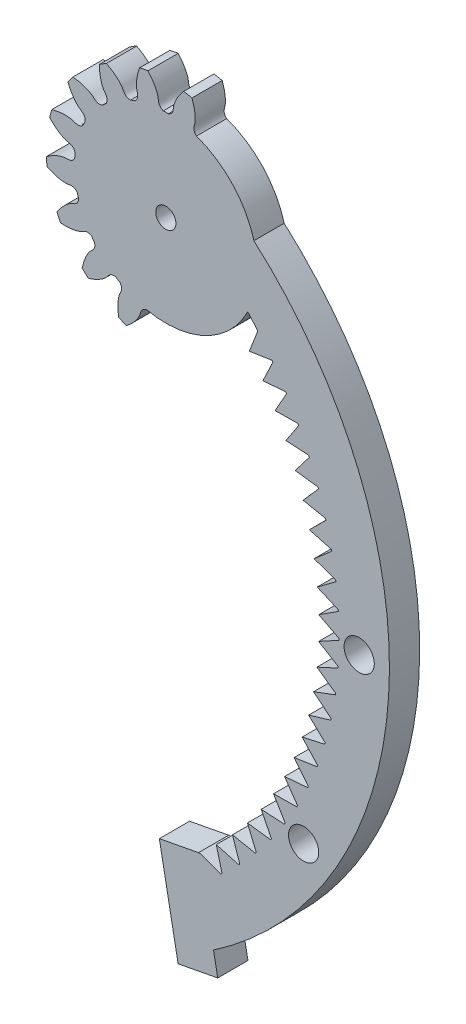
SolidWorks part; units mm, degrees
ref_plane "前视基准面" through (0, 0, 0) normal (0, 0, 1) x (1, 0, 0)
ref_plane "上视基准面" through (0, 0, 0) normal (0, 1, 0) x (1, 0, 0)
ref_plane "右视基准面" through (0, 0, 0) normal (1, 0, 0) x (0, 0, -1)
sketch "草图1" plane through (0, 0, 0) normal (0, 0, 1) x (1, 0, 0)
  circle A0 centre (0, 0) radius 11.875
extrude "凸台-拉伸1" add sketch "草图1" along normal blind 30
ref_axis "基准轴1" through (0, 0, -1.5) along (0, 0, 1)
sketch "草图2" plane through (0, 0, 0) normal (0, 0, 1) x (1, 0, 0)
  line L0 (0, 0) -> (0, 11.875) construction
  circle A0 centre (0, 0) radius 11.875 construction
  arc A1 (0.2521, 9.059) -> (-0.2521, 9.059) centre (0, 0) ccw
  arc A2 (3.8946, 13.4259) -> (-3.8946, 13.4259) centre (0, 0) ccw
  spline S0 degree 3 poles (0.2521, 9.059) (0.7848, 9.281) (0.7077, 9.6935) (0.7979, 10.081) (0.8062, 10.1139) (0.8163, 10.1505) (0.8282, 10.1907) (0.8421, 10.2345) (0.8582, 10.2818) (0.8766, 10.3324) (0.8974, 10.3865) (0.9208, 10.4438) (0.947, 10.5043) (0.976, 10.5679) (1.008, 10.6345) (1.0431, 10.704) (1.0815, 10.7763) (1.1232, 10.8513) (1.1685, 10.929) (1.2174, 11.0091) (1.27, 11.0916) (1.3265, 11.1763) (1.3869, 11.2632) (1.4514, 11.3521) (1.5201, 11.4429) (1.5931, 11.5354) (1.6704, 11.6295) (1.7522, 11.7251) (1.8386, 11.822) (1.9295, 11.9201) (2.0252, 12.0192) (2.1257, 12.1193) (2.2311, 12.22) (2.3414, 12.3213) (2.4567, 12.4231) (2.577, 12.5251) (2.7025, 12.6272) (2.8331, 12.7292) (2.969, 12.831) (3.1101, 12.9323) (3.2564, 13.0331) (3.4081, 13.1332) (3.6198, 13.2668) (3.7832, 13.3632) (3.8946, 13.4259) knots 0 0 0 0 0.193883 0.199024 0.204851 0.211363 0.21856 0.226443 0.235011 0.244265 0.254205 0.264829 0.27614 0.288136 0.300817 0.314184 0.328236 0.342973 0.358397 0.374505 0.391299 0.408779 0.426944 0.445795 0.465331 0.485552 0.506459 0.528051 0.550329 0.573293 0.596941 0.621276 0.646296 0.672001 0.698392 0.725468 0.753229 0.781677 0.810809 0.840627 0.871131 0.90232 0.934195 1 1 1 1
  spline S1 degree 3 poles (-0.2521, 9.059) (-0.7848, 9.281) (-0.7077, 9.6935) (-0.7979, 10.081) (-0.8062, 10.1139) (-0.8163, 10.1505) (-0.8282, 10.1907) (-0.8421, 10.2345) (-0.8582, 10.2818) (-0.8766, 10.3324) (-0.8974, 10.3865) (-0.9208, 10.4438) (-0.947, 10.5043) (-0.976, 10.5679) (-1.008, 10.6345) (-1.0431, 10.704) (-1.0815, 10.7763) (-1.1232, 10.8513) (-1.1685, 10.929) (-1.2174, 11.0091) (-1.27, 11.0916) (-1.3265, 11.1763) (-1.3869, 11.2632) (-1.4514, 11.3521) (-1.5201, 11.4429) (-1.5931, 11.5354) (-1.6704, 11.6295) (-1.7522, 11.7251) (-1.8386, 11.822) (-1.9295, 11.9201) (-2.0252, 12.0192) (-2.1257, 12.1193) (-2.2311, 12.22) (-2.3414, 12.3213) (-2.4567, 12.4231) (-2.577, 12.5251) (-2.7025, 12.6272) (-2.8331, 12.7292) (-2.969, 12.831) (-3.1101, 12.9323) (-3.2564, 13.0331) (-3.4081, 13.1332) (-3.6198, 13.2668) (-3.7832, 13.3632) (-3.8946, 13.4259) knots 0 0 0 0 0.193883 0.199024 0.204851 0.211363 0.21856 0.226443 0.235011 0.244265 0.254205 0.264829 0.27614 0.288136 0.300817 0.314184 0.328236 0.342973 0.358397 0.374505 0.391299 0.408779 0.426944 0.445795 0.465331 0.485552 0.506459 0.528051 0.550329 0.573293 0.596941 0.621276 0.646296 0.672001 0.698392 0.725468 0.753229 0.781677 0.810809 0.840627 0.871131 0.90232 0.934195 1 1 1 1
extrude "切除-拉伸1" cut sketch "草图2" along normal through all
pattern_circular "阵列(圆周)1" count 17 every 21.176 about axis through (0, 0, -1.5) along (0, 0, 1) of "切除-拉伸1"
sketch "草图3" plane through (0, 0, 0) normal (0, 0, 1) x (1, 0, 0)
  circle A0 centre (0, 0) radius 10.625 construction
  dimension "Dn" = 21.25
sketch "草图4" plane through (0, 0, 0) normal (0, 1, 0) x (1, 0, 0)
  line L0 (6.2893, -30) -> (9.2176, -30) construction
  line L1 (-17.9431, 27) -> (17.9431, 27)
  line L2 (-17.9431, 27) -> (-17.9431, -27)
  line L3 (-17.9431, -27) -> (17.9431, -27)
  line L4 (17.9431, 27) -> (17.9431, -27)
  line L5 (-17.9431, 27) -> (17.9431, -27) construction
  line L6 (-17.9431, -27) -> (17.9431, 27) construction
  point P0 (0, 0)
  dimension "D1" = 3
extrude "切除-拉伸2" cut sketch "草图4" against normal through all both and the other way through all
sketch "草图5" plane through (0, 0, 27) normal (0, 0, -1) x (-1, 0, 0)
  arc A0 (-3.5076, 8.3562) -> (1.4168, -8.9511) centre (0, 0) ccw
  arc A34 (-1.9124, -8.8584) -> (-1.4168, -8.9511) centre (0, 0) ccw
  arc A35 (-0.4197, -11.8676) -> (0.4197, -11.8676) centre (0, 0) ccw
  arc A36 (1.4168, -8.9511) -> (1.9124, -8.8584) centre (0, 0) ccw
  arc A37 (3.8958, -11.2178) -> (4.6784, -10.9146) centre (0, 0) ccw
  arc A38 (4.5546, -7.8348) -> (4.9833, -7.5694) centre (0, 0) ccw
  arc A39 (7.685, -9.053) -> (8.3053, -8.4875) centre (0, 0) ccw
  arc A40 (7.0773, -5.6605) -> (7.3812, -5.2581) centre (0, 0) ccw
  arc A41 (10.4364, -5.6655) -> (10.8105, -4.9142) centre (0, 0) ccw
  arc A42 (8.6442, -2.7216) -> (8.7822, -2.2366) centre (0, 0) ccw
  arc A43 (11.7782, -1.5129) -> (11.8557, -0.6771) centre (0, 0) ccw
  arc A44 (9.0436, 0.5848) -> (8.9971, 1.0869) centre (0, 0) ccw
  arc A45 (11.5294, 2.8441) -> (11.2997, 3.6513) centre (0, 0) ccw
  arc A46 (8.2217, 3.8123) -> (7.9969, 4.2636) centre (0, 0) ccw
  arc A47 (9.7234, 6.8169) -> (9.2176, 7.4867) centre (0, 0) ccw
  arc A48 (6.2893, 6.5248) -> (5.9167, 6.8645) centre (0, 0) ccw
  arc A49 (6.6043, 9.8691) -> (5.8907, 10.3109) centre (0, 0) ccw
  arc A50 (3.5076, 8.3562) -> (3.0374, 8.5383) centre (0, 0) ccw
  arc A51 (2.5932, 11.5884) -> (1.7682, 11.7426) centre (0, 0) ccw
  arc A52 (0.2521, 9.059) -> (-0.2521, 9.059) centre (0, 0) ccw
  arc A53 (-1.7682, 11.7426) -> (-2.5932, 11.5884) centre (0, 0) ccw
  arc A54 (-3.0374, 8.5383) -> (-3.5076, 8.3562) centre (0, 0) ccw
  arc A55 (-5.8907, 10.3109) -> (-6.6043, 9.8691) centre (0, 0) ccw
  arc A56 (-5.9167, 6.8645) -> (-6.2893, 6.5248) centre (0, 0) ccw
  arc A57 (-9.2176, 7.4867) -> (-9.7234, 6.8169) centre (0, 0) ccw
  arc A58 (-7.9969, 4.2636) -> (-8.2217, 3.8123) centre (0, 0) ccw
  arc A59 (-11.2997, 3.6513) -> (-11.5294, 2.8441) centre (0, 0) ccw
  arc A60 (-8.9971, 1.0869) -> (-9.0436, 0.5848) centre (0, 0) ccw
  arc A61 (-11.8557, -0.6771) -> (-11.7782, -1.5129) centre (0, 0) ccw
  arc A62 (-8.7822, -2.2366) -> (-8.6442, -2.7216) centre (0, 0) ccw
  arc A63 (-10.8105, -4.9142) -> (-10.4364, -5.6655) centre (0, 0) ccw
  arc A64 (-7.3812, -5.2581) -> (-7.0773, -5.6605) centre (0, 0) ccw
  arc A65 (-8.3053, -8.4875) -> (-7.685, -9.053) centre (0, 0) ccw
  arc A66 (-4.9833, -7.5694) -> (-4.5546, -7.8348) centre (0, 0) ccw
  arc A67 (-4.6784, -10.9146) -> (-3.8958, -11.2178) centre (0, 0) ccw
  arc A68 (-1.9124, -8.8584) -> (-1.4168, -8.9511) centre (0, 0) ccw
  arc A69 (-0.4197, -11.8676) -> (0.4197, -11.8676) centre (0, 0) ccw
  arc A89 (-5.8907, 10.3109) -> (-6.6043, 9.8691) centre (0, 0) ccw
  arc A90 (-5.9167, 6.8645) -> (-6.2893, 6.5248) centre (0, 0) ccw
  arc A91 (-9.2176, 7.4867) -> (-9.7234, 6.8169) centre (0, 0) ccw
  arc A92 (-7.9969, 4.2636) -> (-8.2217, 3.8123) centre (0, 0) ccw
  arc A93 (-11.2997, 3.6513) -> (-11.5294, 2.8441) centre (0, 0) ccw
  arc A94 (-8.9971, 1.0869) -> (-9.0436, 0.5848) centre (0, 0) ccw
  arc A95 (-11.8557, -0.6771) -> (-11.7782, -1.5129) centre (0, 0) ccw
  arc A96 (-8.7822, -2.2366) -> (-8.6442, -2.7216) centre (0, 0) ccw
  arc A97 (-10.8105, -4.9142) -> (-10.4364, -5.6655) centre (0, 0) ccw
  arc A98 (-7.3812, -5.2581) -> (-7.0773, -5.6605) centre (0, 0) ccw
  arc A99 (-8.3053, -8.4875) -> (-7.685, -9.053) centre (0, 0) ccw
  arc A100 (-4.9833, -7.5694) -> (-4.5546, -7.8348) centre (0, 0) ccw
  arc A101 (-4.6784, -10.9146) -> (-3.8958, -11.2178) centre (0, 0) ccw
  spline S34 degree 3 poles (3846.6872, -1092.6583) (-166.0819, 94.8519) (-23.9952, -29.1385) (-3.5148, -10.8956) (-3.3596, -10.7459) (-3.2216, -10.6015) (-3.1, -10.4638) (-2.994, -10.3337) (-2.903, -10.2123) (-2.8259, -10.1004) (-2.7618, -9.9992) (-2.7099, -9.9092) (-2.669, -9.8315) (-2.6418, -9.7744) (-0.0037, -3.7598) (-41.8709, 21.0457) (3590.3113, -1767.5712) knots -13.52866 -13.52866 -13.52866 -13.52866 0.514448 0.554205 0.591221 0.625495 0.657027 0.685816 0.711864 0.735171 0.755735 0.773557 0.788637 0.800976 0.806117 4.170224 4.170224 4.170224 4.170224 only from (-3.8958, -11.2178) to (-1.9124, -8.8584)
  spline S35 degree 3 poles (-3986.5533, -351.2558) (46.6474, 4.4992) (-1.3547, -3.5071) (-1.0675, -10.0686) (-1.0628, -10.1317) (-1.0527, -10.219) (-1.0368, -10.3216) (-1.0137, -10.4392) (-0.9822, -10.5713) (-0.9411, -10.7174) (-0.8893, -10.877) (-0.8257, -11.0494) (-0.7491, -11.2338) (-0.6585, -11.4296) (11.8561, -35.8532) (189.3273, 28.5276) (-3981.6102, 370.5232) knots -3.17027 -3.17027 -3.17027 -3.17027 0.193883 0.199024 0.211363 0.226443 0.244265 0.264829 0.288136 0.314184 0.342973 0.374505 0.408779 0.445795 0.485552 14.536898 14.536898 14.536898 14.536898 only from (-1.4168, -8.9511) to (-0.4197, -11.8676)
  spline S36 degree 3 poles (3981.6427, 370.7101) (-189.1312, 28.4511) (-11.8488, -35.8389) (0.6585, -11.4296) (0.7491, -11.2338) (0.8257, -11.0494) (0.8893, -10.877) (0.9411, -10.7174) (0.9822, -10.5713) (1.0137, -10.4392) (1.0368, -10.3216) (1.0527, -10.219) (1.0628, -10.1317) (1.0675, -10.0686) (1.3547, -3.5072) (-46.646, 4.499) (3986.386, -351.241) knots -13.52866 -13.52866 -13.52866 -13.52866 0.514448 0.554205 0.591221 0.625495 0.657027 0.685816 0.711864 0.735171 0.755735 0.773557 0.788637 0.800976 0.806117 4.170224 4.170224 4.170224 4.170224 only from (0.4197, -11.8676) to (1.4168, -8.9511)
  spline S37 degree 3 poles (-898.5927, -443.6949) (17.2399, 5.4469) (0.9629, -5.9466) (2.6418, -9.7744) (2.669, -9.8315) (2.7099, -9.9092) (2.7618, -9.9992) (2.8259, -10.1004) (2.903, -10.2123) (2.994, -10.3337) (3.1, -10.4638) (3.2216, -10.6015) (3.3596, -10.7459) (3.5148, -10.8956) (16.8216, -22.7486) (81.2838, 25.299) (-964.1727, -261.9023) knots -1.94072 -1.94072 -1.94072 -1.94072 0.193883 0.199024 0.211363 0.226443 0.244265 0.264829 0.288136 0.314184 0.342973 0.374505 0.408779 0.445795 0.485552 9.582933 9.582933 9.582933 9.582933 only from (1.9124, -8.8584) to (3.8958, -11.2178)
  spline S38 degree 3 poles (888.9695, 456.0196) (-77.0192, -36.0568) (2.8955, -28.1332) (4.7428, -10.4199) (4.7566, -10.2046) (4.7614, -10.005) (4.7585, -9.8213) (4.7492, -9.6538) (4.7346, -9.5027) (4.7163, -9.3681) (4.6954, -9.2501) (4.6732, -9.1486) (4.651, -9.0636) (4.6327, -9.0031) (3.2946, -5.0433) (-16.4094, -7.589) (962.9381, 277.4704) knots -8.57732 -8.57732 -8.57732 -8.57732 0.514448 0.554205 0.591221 0.625495 0.657027 0.685816 0.711864 0.735171 0.755735 0.773557 0.788637 0.800976 0.806117 2.940687 2.940687 2.940687 2.940687 only from (4.6784, -10.9146) to (4.5546, -7.8348)
  spline S39 degree 3 poles (-677.6317, -738.3423) (14.1081, 11.3069) (3.046, -5.1972) (5.9943, -8.16) (6.0403, -8.2034) (6.1065, -8.2612) (6.1874, -8.3262) (6.2837, -8.3976) (6.396, -8.474) (6.5248, -8.5543) (6.6706, -8.6374) (6.8337, -8.7219) (7.0146, -8.8066) (7.2135, -8.8902) (23.9034, -15.1358) (66.6558, 52.9537) (-804.4542, -592.516) knots -1.94072 -1.94072 -1.94072 -1.94072 0.193883 0.199024 0.211363 0.226443 0.244265 0.264829 0.288136 0.314184 0.342973 0.374505 0.408779 0.445795 0.485552 9.582933 9.582933 9.582933 9.582933 only from (4.9833, -7.5694) to (7.685, -9.053)
  spline S40 degree 3 poles (664.2061, 746.3584) (-58.7931, -61.4445) (12.8629, -25.1875) (8.1867, -8.003) (8.1218, -7.7973) (8.0541, -7.6093) (7.985, -7.4391) (7.9158, -7.2863) (7.8477, -7.1506) (7.7819, -7.0318) (7.7198, -6.9293) (7.6625, -6.8427) (7.6111, -6.7714) (7.5721, -6.7216) (4.894, -3.5126) (-12.5599, -13.0043) (797.6792, 606.5868) knots -8.57732 -8.57732 -8.57732 -8.57732 0.514448 0.554205 0.591221 0.625495 0.657027 0.685816 0.711864 0.735171 0.755735 0.773557 0.788637 0.800976 0.806117 2.940687 2.940687 2.940687 2.940687 only from (8.3053, -8.4875) to (7.0773, -5.6605)
  spline S41 degree 3 poles (-365.1527, -933.2725) (9.0709, 15.6398) (4.7178, -3.7459) (8.5372, -5.4436) (8.5958, -5.4675) (8.6784, -5.4974) (8.7774, -5.5288) (8.893, -5.5605) (9.0253, -5.5912) (9.1744, -5.6196) (9.3403, -5.6444) (9.523, -5.6643) (9.7222, -5.6779) (9.9378, -5.684) (27.757, -5.4788) (43.0256, 73.4567) (-536.0897, -843.1071) knots -1.94072 -1.94072 -1.94072 -1.94072 0.193883 0.199024 0.211363 0.226443 0.244265 0.264829 0.288136 0.314184 0.342973 0.374505 0.408779 0.445795 0.485552 9.582933 9.582933 9.582933 9.582933 only from (7.3812, -5.2581) to (10.4364, -5.6655)
  spline S42 degree 3 poles (349.7379, 935.8974) (-32.6266, -78.5338) (21.093, -18.84) (10.5249, -4.5052) (10.39, -4.3368) (10.2591, -4.186) (10.1331, -4.0522) (10.0134, -3.9347) (9.9008, -3.8328) (9.7966, -3.7458) (9.7017, -3.6727) (9.6169, -3.6126) (9.5433, -3.5647) (9.4889, -3.5324) (5.8324, -1.5075) (-7.014, -16.6633) (524.6893, 853.7803) knots -8.57732 -8.57732 -8.57732 -8.57732 0.514448 0.554205 0.591221 0.625495 0.657027 0.685816 0.711864 0.735171 0.755735 0.773557 0.788637 0.800976 0.806117 2.940687 2.940687 2.940687 2.940687 only from (10.8105, -4.9142) to (8.6442, -2.7216)
  spline S43 degree 3 poles (-3.3579, -1002.1591) (2.8086, 17.8605) (5.7524, -1.7887) (9.9272, -1.992) (9.9904, -1.9931) (10.0783, -1.9911) (10.1819, -1.9847) (10.3011, -1.9725) (10.4356, -1.9534) (10.5849, -1.926) (10.7486, -1.8891) (10.9261, -1.8417) (11.1168, -1.7824) (11.3201, -1.7102) (27.8618, 4.9181) (13.5846, 84.039) (-195.3234, -979.8319) knots -1.94072 -1.94072 -1.94072 -1.94072 0.193883 0.199024 0.211363 0.226443 0.244265 0.264829 0.288136 0.314184 0.342973 0.374505 0.408779 0.445795 0.485552 9.582933 9.582933 9.582933 9.582933 only from (8.7822, -2.2366) to (11.7782, -1.5129)
  spline S44 degree 3 poles (-11.9642, 999.0383) (-2.0537, -85.0167) (26.4745, -9.9481) (11.4416, -0.3989) (11.255, -0.2906) (11.0784, -0.1973) (10.9127, -0.1181) (10.7586, -0.0518) (10.6168, 0.0026) (10.4882, 0.0461) (10.3733, 0.08) (10.2725, 0.1054) (10.1865, 0.1234) (10.1242, 0.134) (5.9832, 0.7012) (-0.5209, -18.0718) (180.8372, 985.666) knots -8.57732 -8.57732 -8.57732 -8.57732 0.514448 0.554205 0.591221 0.625495 0.657027 0.685816 0.711864 0.735171 0.755735 0.773557 0.788637 0.800976 0.806117 2.940687 2.940687 2.940687 2.940687 only from (11.8557, -0.6771) to (9.0436, 0.5848)
  spline S45 degree 3 poles (358.8905, -935.6985) (-3.833, 17.669) (6.0101, 0.4101) (9.9764, 1.7286) (10.0358, 1.7504) (10.117, 1.784) (10.2113, 1.8274) (10.3181, 1.8819) (10.4365, 1.9483) (10.5659, 2.0278) (10.7052, 2.1213) (10.8536, 2.2296) (11.01, 2.3538) (11.1735, 2.4945) (24.2037, 14.6509) (-17.6912, 83.2713) (171.8225, -984.225) knots -1.94072 -1.94072 -1.94072 -1.94072 0.193883 0.199024 0.211363 0.226443 0.244265 0.264829 0.288136 0.314184 0.342973 0.374505 0.408779 0.445795 0.485552 9.582933 9.582933 9.582933 9.582933 only from (8.9971, 1.0869) to (11.5294, 2.8441)
  spline S46 degree 3 poles (-372.0506, 927.2535) (28.7965, -80.0176) (28.2804, 0.2873) (10.8131, 3.7612) (10.6, 3.7948) (10.4016, 3.818) (10.2184, 3.832) (10.0508, 3.8382) (9.899, 3.8377) (9.7633, 3.8318) (9.6439, 3.8218) (9.5408, 3.8091) (9.4541, 3.7949) (9.3921, 3.7822) (5.3258, 2.8153) (6.0426, -17.0397) (-187.438, 984.4321) knots -8.57732 -8.57732 -8.57732 -8.57732 0.514448 0.554205 0.591221 0.625495 0.657027 0.685816 0.711864 0.735171 0.755735 0.773557 0.788637 0.800976 0.806117 2.940687 2.940687 2.940687 2.940687 only from (11.2997, 3.6513) to (8.2217, 3.8123)
  spline S47 degree 3 poles (672.6687, -742.8667) (-9.9569, 15.0912) (5.4561, 2.5535) (8.6783, 5.2158) (8.7257, 5.2576) (8.7894, 5.3182) (8.8616, 5.3928) (8.9415, 5.4821) (9.028, 5.5869) (9.1199, 5.7077) (9.216, 5.8452) (9.3152, 5.9998) (9.4162, 6.1721) (9.5178, 6.3624) (17.2768, 22.4049) (-46.5776, 71.2574) (515.7628, -855.693) knots -1.94072 -1.94072 -1.94072 -1.94072 0.193883 0.199024 0.211363 0.226443 0.244265 0.264829 0.288136 0.314184 0.342973 0.374505 0.408779 0.445795 0.485552 9.582933 9.582933 9.582933 9.582933 only from (7.9969, 4.2636) to (9.7234, 6.8169)
  spline S48 degree 3 poles (-681.8894, 730.2379) (55.7577, -64.2117) (26.2669, 10.484) (8.7242, 7.4133) (8.5134, 7.3677) (8.32, 7.3177) (8.1441, 7.2646) (7.9856, 7.2097) (7.8442, 7.1544) (7.7198, 7.0999) (7.612, 7.0475) (7.5205, 6.9984) (7.4448, 6.9538) (7.3916, 6.9196) (3.9492, 4.5491) (11.79, -13.7062) (-530.3986, 850.2452) knots -8.57732 -8.57732 -8.57732 -8.57732 0.514448 0.554205 0.591221 0.625495 0.657027 0.685816 0.711864 0.735171 0.755735 0.773557 0.788637 0.800976 0.806117 2.940687 2.940687 2.940687 2.940687 only from (9.2176, 7.4867) to (6.2893, 6.5248)
  spline S49 degree 3 poles (895.5993, -449.7066) (-14.7361, 10.4752) (4.1652, 4.352) (6.2081, 7.9985) (6.2373, 8.0546) (6.2747, 8.1342) (6.3151, 8.2298) (6.3574, 8.342) (6.4001, 8.4709) (6.4422, 8.6167) (6.4821, 8.7797) (6.5188, 8.9597) (6.5507, 9.1569) (6.5767, 9.371) (8.0165, 27.1331) (-69.1734, 49.6198) (790.0464, -611.595) knots -1.94072 -1.94072 -1.94072 -1.94072 0.193883 0.199024 0.211363 0.226443 0.244265 0.264829 0.288136 0.314184 0.342973 0.374505 0.408779 0.445795 0.485552 9.582933 9.582933 9.582933 9.582933 only from (5.9167, 6.8645) to (6.6043, 9.8691)
  spline S50 degree 3 poles (-899.6353, 434.5997) (75.1884, -39.7336) (20.7059, 19.2647) (5.4571, 10.0643) (5.277, 9.9456) (5.1147, 9.8291) (4.9699, 9.716) (4.8419, 9.6076) (4.73, 9.505) (4.6337, 9.4092) (4.5521, 9.3214) (4.4845, 9.2426) (4.43, 9.1736) (4.3928, 9.1225) (2.0392, 5.6685) (15.9451, -8.5216) (-801.726, 601.2279) knots -8.57732 -8.57732 -8.57732 -8.57732 0.514448 0.554205 0.591221 0.625495 0.657027 0.685816 0.711864 0.735171 0.755735 0.773557 0.788637 0.800976 0.806117 2.940687 2.940687 2.940687 2.940687 only from (5.8907, 10.3109) to (3.5076, 8.3562)
  spline S51 degree 3 poles (997.5742, -95.8111) (-17.5251, 4.4446) (2.3118, 5.5628) (2.8995, 9.701) (2.9064, 9.7639) (2.9126, 9.8516) (2.9157, 9.9554) (2.9146, 10.0752) (2.9079, 10.2108) (2.8944, 10.362) (2.8728, 10.5284) (2.842, 10.7095) (2.8005, 10.9049) (2.7474, 11.114) (-2.3264, 28.1967) (-82.427, 21.2807) (957.63, -284.8976) knots -1.94072 -1.94072 -1.94072 -1.94072 0.193883 0.199024 0.211363 0.226443 0.244265 0.264829 0.288136 0.314184 0.342973 0.374505 0.408779 0.445795 0.485552 9.582933 9.582933 9.582933 9.582933 only from (3.0374, 8.5383) to (2.5932, 11.5884)
  spline S52 degree 3 poles (-995.8805, 80.2664) (84.4645, -9.8893) (12.3484, 25.4436) (1.4529, 11.356) (1.3279, 11.1802) (1.2187, 11.013) (1.1245, 10.8552) (1.0442, 10.7079) (0.977, 10.5718) (0.9218, 10.4477) (0.8775, 10.3364) (0.8429, 10.2384) (0.817, 10.1545) (0.8007, 10.0933) (-0.1462, 6.0223) (17.9467, -2.1861) (-964.7758, 271.0115) knots -8.57732 -8.57732 -8.57732 -8.57732 0.514448 0.554205 0.591221 0.625495 0.657027 0.685816 0.711864 0.735171 0.755735 0.773557 0.788637 0.800976 0.806117 2.940687 2.940687 2.940687 2.940687 only from (1.7682, 11.7426) to (0.2521, 9.059)
  spline S53 degree 3 poles (964.8212, 271.0241) (-17.9472, -2.1864) (0.1462, 6.0223) (-0.8007, 10.0933) (-0.817, 10.1545) (-0.8429, 10.2384) (-0.8775, 10.3364) (-0.9218, 10.4477) (-0.977, 10.5718) (-1.0442, 10.7079) (-1.1245, 10.8552) (-1.2187, 11.013) (-1.3279, 11.1802) (-1.4529, 11.356) (-12.3551, 25.4523) (-84.5484, -9.9324) (995.8802, 80.2767) knots -1.94072 -1.94072 -1.94072 -1.94072 0.193883 0.199024 0.211363 0.226443 0.244265 0.264829 0.288136 0.314184 0.342973 0.374505 0.408779 0.445795 0.485552 9.582933 9.582933 9.582933 9.582933 only from (-0.2521, 9.059) to (-1.7682, 11.7426)
  spline S54 degree 3 poles (-957.6265, -284.9073) (82.3333, 21.2906) (2.3233, 28.1863) (-2.7474, 11.114) (-2.8005, 10.9049) (-2.842, 10.7095) (-2.8728, 10.5284) (-2.8944, 10.362) (-2.9079, 10.2108) (-2.9146, 10.0752) (-2.9157, 9.9554) (-2.9126, 9.8516) (-2.9064, 9.7639) (-2.8995, 9.701) (-2.3118, 5.5629) (17.5245, 4.4446) (-997.5273, -95.8065) knots -8.57732 -8.57732 -8.57732 -8.57732 0.514448 0.554205 0.591221 0.625495 0.657027 0.685816 0.711864 0.735171 0.755735 0.773557 0.788637 0.800976 0.806117 2.940687 2.940687 2.940687 2.940687 only from (-2.5932, 11.5884) to (-3.0374, 8.5383)
  spline S55 degree 3 poles (3204.5235, 2397.2936) (-37.2918, -28.382) (-0.6945, 3.695) (-4.3928, 9.1225) (-4.43, 9.1736) (-4.4845, 9.2426) (-4.5521, 9.3214) (-4.6337, 9.4092) (-4.73, 9.505) (-4.8419, 9.6076) (-4.9699, 9.716) (-5.1147, 9.8291) (-5.277, 9.9456) (-5.4571, 10.0643) (-28.9545, 24.2415) (-145.9515, -123.9226) (3580.2885, 1781.0225) knots -3.17027 -3.17027 -3.17027 -3.17027 0.193883 0.199024 0.211363 0.226443 0.244265 0.264829 0.288136 0.314184 0.342973 0.374505 0.408779 0.445795 0.485552 14.536898 14.536898 14.536898 14.536898 only from (-3.5076, 8.3562) to (-5.8907, 10.3109)
  spline S56 degree 3 poles (-3190.1071, -2411.2489) (175.7802, 75.3751) (-8.7927, 36.7085) (-6.5767, 9.371) (-6.5507, 9.1569) (-6.5188, 8.9597) (-6.4821, 8.7797) (-6.4422, 8.6167) (-6.4001, 8.4709) (-6.3574, 8.342) (-6.3151, 8.2298) (-6.2747, 8.1342) (-6.2373, 8.0546) (-6.2081, 7.9985) (-2.9981, 2.2687) (42.0277, 20.7308) (-3574.1983, -1799.9306) knots -13.52866 -13.52866 -13.52866 -13.52866 0.514448 0.554205 0.591221 0.625495 0.657027 0.685816 0.711864 0.735171 0.755735 0.773557 0.788637 0.800976 0.806117 4.170224 4.170224 4.170224 4.170224 only from (-6.6043, 9.8691) to (-5.9167, 6.8645)
  spline S57 degree 3 poles (2122.1269, 3393.0171) (-24.5208, -39.9368) (-1.9823, 3.1946) (-7.3916, 6.9196) (-7.4448, 6.9538) (-7.5205, 6.9984) (-7.612, 7.0475) (-7.7198, 7.0999) (-7.8442, 7.1544) (-7.9856, 7.2097) (-8.1441, 7.2646) (-8.32, 7.3177) (-8.5134, 7.3677) (-8.7242, 7.4133) (-35.7563, 12.145) (-91.3297, -168.2782) (2695.1401, 2954.1034) knots -3.17027 -3.17027 -3.17027 -3.17027 0.193883 0.199024 0.211363 0.226443 0.244265 0.264829 0.288136 0.314184 0.342973 0.374505 0.408779 0.445795 0.485552 14.536898 14.536898 14.536898 14.536898 only from (-6.2893, 6.5248) to (-9.2176, 7.4867)
  spline S58 degree 3 poles (-2103.6427, -3400.8222) (136.6815, 133.7844) (-21.4596, 31.0533) (-9.5178, 6.3624) (-9.4162, 6.1721) (-9.3152, 5.9998) (-9.216, 5.8452) (-9.1199, 5.7077) (-9.028, 5.5869) (-8.9415, 5.4821) (-8.8616, 5.3928) (-8.7894, 5.3182) (-8.7257, 5.2576) (-8.6783, 5.2158) (-3.6152, 1.0325) (31.7008, 34.5131) (-2682.6307, -2969.5347) knots -13.52866 -13.52866 -13.52866 -13.52866 0.514448 0.554205 0.591221 0.625495 0.657027 0.685816 0.711864 0.735171 0.755735 0.773557 0.788637 0.800976 0.806117 4.170224 4.170224 4.170224 4.170224 only from (-9.7234, 6.8169) to (-7.9969, 4.2636)
  spline S59 degree 3 poles (753.1252, 3930.4949) (-8.4382, -46.0979) (-3.0025, 2.2628) (-9.3921, 3.7822) (-9.4541, 3.7949) (-9.5408, 3.8091) (-9.6439, 3.8218) (-9.7633, 3.8318) (-9.899, 3.8377) (-10.0508, 3.8382) (-10.2184, 3.832) (-10.4016, 3.818) (-10.6, 3.7948) (-10.8131, 3.7612) (-37.7291, -1.5918) (-24.3733, -189.9068) (1445.998, 3728.2163) knots -3.17027 -3.17027 -3.17027 -3.17027 0.193883 0.199024 0.211363 0.226443 0.244265 0.264829 0.288136 0.314184 0.342973 0.374505 0.408779 0.445795 0.485552 14.536898 14.536898 14.536898 14.536898 only from (-8.2217, 3.8123) to (-11.2997, 3.6513)
  spline S60 degree 3 poles (-733.0697, -3931.0957) (79.1232, 174.1253) (-31.2282, 21.2042) (-11.1735, 2.4945) (-11.01, 2.3538) (-10.8536, 2.2296) (-10.7052, 2.1213) (-10.5659, 2.0278) (-10.4365, 1.9483) (-10.3181, 1.8819) (-10.2113, 1.8274) (-10.117, 1.784) (-10.0358, 1.7504) (-9.9764, 1.7286) (-3.7441, -0.3432) (17.0926, 43.6341) (-1428.759, -3738.0866) knots -13.52866 -13.52866 -13.52866 -13.52866 0.514448 0.554205 0.591221 0.625495 0.657027 0.685816 0.711864 0.735171 0.755735 0.773557 0.788637 0.800976 0.806117 4.170224 4.170224 4.170224 4.170224 only from (-11.5294, 2.8441) to (-8.9971, 1.0869)
  spline S61 degree 3 poles (-717.5901, 3937.1375) (8.7841, -46.0332) (-3.6172, 1.0254) (-10.1242, 0.134) (-10.1865, 0.1234) (-10.2725, 0.1054) (-10.3733, 0.08) (-10.4882, 0.0461) (-10.6168, 0.0026) (-10.7586, -0.0518) (-10.9127, -0.1181) (-11.0784, -0.1973) (-11.255, -0.2906) (-11.4416, -0.3989) (-34.6063, -15.1136) (45.8748, -185.8875) (1.5659, 3998.8129) knots -3.17027 -3.17027 -3.17027 -3.17027 0.193883 0.199024 0.211363 0.226443 0.244265 0.264829 0.288136 0.314184 0.342973 0.374505 0.408779 0.445795 0.485552 14.536898 14.536898 14.536898 14.536898 only from (-9.0436, 0.5848) to (-11.8557, -0.6771)
  spline S62 degree 3 poles (736.5084, -3930.4529) (10.8789, 190.9496) (-36.7793, 8.4914) (-11.3201, -1.7102) (-11.1168, -1.7824) (-10.9261, -1.8417) (-10.7486, -1.8891) (-10.5849, -1.926) (-10.4356, -1.9534) (-10.3011, -1.9725) (-10.1819, -1.9847) (-10.0783, -1.9911) (-9.9904, -1.9931) (-9.9272, -1.992) (-3.3673, -1.6726) (0.1759, 46.8622) (18.0746, -4001.7892) knots -13.52866 -13.52866 -13.52866 -13.52866 0.514448 0.554205 0.591221 0.625495 0.657027 0.685816 0.711864 0.735171 0.755735 0.773557 0.788637 0.800976 0.806117 4.170224 4.170224 4.170224 4.170224 only from (-11.7782, -1.5129) to (-8.7822, -2.2366)
  spline S63 degree 3 poles (-2091.391, 3412.048) (24.8201, -39.7515) (-3.7433, -0.3506) (-9.4889, -3.5324) (-9.5433, -3.5647) (-9.6169, -3.6126) (-9.7017, -3.6727) (-9.7966, -3.7458) (-9.9008, -3.8328) (-10.0134, -3.9347) (-10.1331, -4.0522) (-10.2591, -4.186) (-10.39, -4.3368) (-10.5249, -4.5052) (-26.8097, -26.5943) (109.9273, -156.7631) (-1443.0776, 3729.3477) knots -3.17027 -3.17027 -3.17027 -3.17027 0.193883 0.199024 0.211363 0.226443 0.244265 0.264829 0.288136 0.314184 0.342973 0.374505 0.408779 0.445795 0.485552 14.536898 14.536898 14.536898 14.536898 only from (-8.6442, -2.7216) to (-10.8105, -4.9142)
  spline S64 degree 3 poles (2106.617, -3398.9806) (-58.8347, 181.9851) (-37.3631, -5.3682) (-9.9378, -5.684) (-9.7222, -5.6779) (-9.523, -5.6643) (-9.3403, -5.6444) (-9.1744, -5.6196) (-9.0253, -5.5912) (-8.893, -5.5605) (-8.7774, -5.5288) (-8.6784, -5.4974) (-8.5958, -5.4675) (-8.5372, -5.4436) (-2.5357, -2.776) (-16.7646, 43.7612) (1462.467, -3725.028) knots -13.52866 -13.52866 -13.52866 -13.52866 0.514448 0.554205 0.591221 0.625495 0.657027 0.685816 0.711864 0.735171 0.755735 0.773557 0.788637 0.800976 0.806117 4.170224 4.170224 4.170224 4.170224 only from (-10.4364, -5.6655) to (-7.3812, -5.2581)
  spline S65 degree 3 poles (-3182.7379, 2426.1424) (37.5039, -28.1012) (-3.3639, -1.6791) (-7.5721, -6.7216) (-7.6111, -6.7714) (-7.6625, -6.8427) (-7.7198, -6.9293) (-7.7819, -7.0318) (-7.8477, -7.1506) (-7.9158, -7.2863) (-7.985, -7.4391) (-8.0541, -7.6093) (-8.1218, -7.7973) (-8.1867, -8.003) (-15.3924, -34.4832) (159.1335, -106.4669) (-2692.8256, 2956.2134) knots -3.17027 -3.17027 -3.17027 -3.17027 0.193883 0.199024 0.211363 0.226443 0.244265 0.264829 0.288136 0.314184 0.342973 0.374505 0.408779 0.445795 0.485552 14.536898 14.536898 14.536898 14.536898 only from (-7.0773, -5.6605) to (-8.3053, -8.4875)
  spline S66 degree 3 poles (3192.2152, -2408.4572) (-120.6023, 148.4425) (-32.9009, -18.5028) (-7.2135, -8.8902) (-7.0146, -8.8066) (-6.8337, -8.7219) (-6.6706, -8.6374) (-6.5248, -8.5543) (-6.396, -8.474) (-6.2837, -8.3976) (-6.1874, -8.3262) (-6.1065, -8.2612) (-6.0403, -8.2034) (-5.9943, -8.16) (-1.3616, -3.5045) (-31.4409, 34.75) (2709.3452, -2945.1811) knots -13.52866 -13.52866 -13.52866 -13.52866 0.514448 0.554205 0.591221 0.625495 0.657027 0.685816 0.711864 0.735171 0.755735 0.773557 0.788637 0.800976 0.806117 4.170224 4.170224 4.170224 4.170224 only from (-7.685, -9.053) to (-4.9833, -7.5694)
  spline S67 degree 3 poles (-3844.2384, 1112.5729) (45.1227, -12.6556) (-2.5302, -2.7809) (-4.6327, -9.0031) (-4.651, -9.0636) (-4.6732, -9.1486) (-4.6954, -9.2501) (-4.7163, -9.3681) (-4.7346, -9.5027) (-4.7492, -9.6538) (-4.7585, -9.8213) (-4.7614, -10.005) (-4.7566, -10.2046) (-4.7428, -10.4199) (-1.8962, -37.715) (186.8478, -41.7918) (-3578.8925, 1783.8261) knots -3.17027 -3.17027 -3.17027 -3.17027 0.193883 0.199024 0.211363 0.226443 0.244265 0.264829 0.288136 0.314184 0.342973 0.374505 0.408779 0.445795 0.485552 14.536898 14.536898 14.536898 14.536898 only from (-4.5546, -7.8348) to (-4.6784, -10.9146)
  spline S68 degree 3 poles (-3.8958, -11.2178) (-3.8242, -11.1617) (-3.6941, -11.0553) (-3.5148, -10.8956) (-3.3596, -10.7459) (-3.2216, -10.6015) (-3.1, -10.4638) (-2.994, -10.3337) (-2.903, -10.2123) (-2.8259, -10.1004) (-2.7618, -9.9992) (-2.7099, -9.9092) (-2.669, -9.8315) (-2.6418, -9.7744) (-2.4769, -9.3984) (-2.4769, -8.9788) (-1.9124, -8.8584) knots 0.467653 0.467653 0.467653 0.467653 0.514448 0.554205 0.591221 0.625495 0.657027 0.685816 0.711864 0.735171 0.755735 0.773557 0.788637 0.800976 0.806117 1 1 1 1
  spline S69 degree 3 poles (-1.4168, -8.9511) (-0.9339, -9.2672) (-1.0855, -9.6585) (-1.0675, -10.0686) (-1.0628, -10.1317) (-1.0527, -10.219) (-1.0368, -10.3216) (-1.0137, -10.4392) (-0.9822, -10.5713) (-0.9411, -10.7174) (-0.8893, -10.877) (-0.8257, -11.0494) (-0.7491, -11.2338) (-0.6585, -11.4296) (-0.549, -11.6432) (-0.4661, -11.7895) (-0.4197, -11.8676) knots 0 0 0 0 0.193883 0.199024 0.211363 0.226443 0.244265 0.264829 0.288136 0.314184 0.342973 0.374505 0.408779 0.445795 0.485552 0.532347 0.532347 0.532347 0.532347
  spline S70 degree 3 poles (0.4197, -11.8676) (0.4661, -11.7895) (0.549, -11.6432) (0.6585, -11.4296) (0.7491, -11.2338) (0.8257, -11.0494) (0.8893, -10.877) (0.9411, -10.7174) (0.9822, -10.5713) (1.0137, -10.4392) (1.0368, -10.3216) (1.0527, -10.219) (1.0628, -10.1317) (1.0675, -10.0686) (1.0855, -9.6585) (0.9339, -9.2672) (1.4168, -8.9511) knots 0.467653 0.467653 0.467653 0.467653 0.514448 0.554205 0.591221 0.625495 0.657027 0.685816 0.711864 0.735171 0.755735 0.773557 0.788637 0.800976 0.806117 1 1 1 1
  spline S89 degree 3 poles (-3.5076, 8.3562) (-4.0845, 8.3708) (-4.1617, 8.7833) (-4.3928, 9.1225) (-4.43, 9.1736) (-4.4845, 9.2426) (-4.5521, 9.3214) (-4.6337, 9.4092) (-4.73, 9.505) (-4.8419, 9.6076) (-4.9699, 9.716) (-5.1147, 9.8291) (-5.277, 9.9456) (-5.4571, 10.0643) (-5.6626, 10.1883) (-5.8101, 10.269) (-5.8907, 10.3109) knots 0 0 0 0 0.193883 0.199024 0.211363 0.226443 0.244265 0.264829 0.288136 0.314184 0.342973 0.374505 0.408779 0.445795 0.485552 0.532347 0.532347 0.532347 0.532347
  spline S90 degree 3 poles (-6.6043, 9.8691) (-6.6027, 9.7782) (-6.5961, 9.6102) (-6.5767, 9.371) (-6.5507, 9.1569) (-6.5188, 8.9597) (-6.4821, 8.7797) (-6.4422, 8.6167) (-6.4001, 8.4709) (-6.3574, 8.342) (-6.3151, 8.2298) (-6.2747, 8.1342) (-6.2373, 8.0546) (-6.2081, 7.9985) (-6.0075, 7.6404) (-5.6726, 7.3875) (-5.9167, 6.8645) knots 0.467653 0.467653 0.467653 0.467653 0.514448 0.554205 0.591221 0.625495 0.657027 0.685816 0.711864 0.735171 0.755735 0.773557 0.788637 0.800976 0.806117 1 1 1 1
  spline S91 degree 3 poles (-6.2893, 6.5248) (-6.8326, 6.33) (-7.0535, 6.6868) (-7.3916, 6.9196) (-7.4448, 6.9538) (-7.5205, 6.9984) (-7.612, 7.0475) (-7.7198, 7.0999) (-7.8442, 7.1544) (-7.9856, 7.2097) (-8.1441, 7.2646) (-8.32, 7.3177) (-8.5134, 7.3677) (-8.7242, 7.4133) (-8.9606, 7.4547) (-9.1273, 7.4767) (-9.2176, 7.4867) knots 0 0 0 0 0.193883 0.199024 0.211363 0.226443 0.244265 0.264829 0.288136 0.314184 0.342973 0.374505 0.408779 0.445795 0.485552 0.532347 0.532347 0.532347 0.532347
  spline S92 degree 3 poles (-9.7234, 6.8169) (-9.6891, 6.7328) (-9.6223, 6.5785) (-9.5178, 6.3624) (-9.4162, 6.1721) (-9.3152, 5.9998) (-9.216, 5.8452) (-9.1199, 5.7077) (-9.028, 5.5869) (-8.9415, 5.4821) (-8.8616, 5.3928) (-8.7894, 5.3182) (-8.7257, 5.2576) (-8.6783, 5.2158) (-8.3618, 4.9543) (-7.9582, 4.8395) (-7.9969, 4.2636) knots 0.467653 0.467653 0.467653 0.467653 0.514448 0.554205 0.591221 0.625495 0.657027 0.685816 0.711864 0.735171 0.755735 0.773557 0.788637 0.800976 0.806117 1 1 1 1
  spline S93 degree 3 poles (-8.2217, 3.8123) (-8.6579, 3.4343) (-8.9927, 3.6872) (-9.3921, 3.7822) (-9.4541, 3.7949) (-9.5408, 3.8091) (-9.6439, 3.8218) (-9.7633, 3.8318) (-9.899, 3.8377) (-10.0508, 3.8382) (-10.2184, 3.832) (-10.4016, 3.818) (-10.6, 3.7948) (-10.8131, 3.7612) (-11.0485, 3.7144) (-11.2119, 3.6747) (-11.2997, 3.6513) knots 0 0 0 0 0.193883 0.199024 0.211363 0.226443 0.244265 0.264829 0.288136 0.314184 0.342973 0.374505 0.408779 0.445795 0.485552 0.532347 0.532347 0.532347 0.532347
  spline S94 degree 3 poles (-11.5294, 2.8441) (-11.467, 2.778) (-11.349, 2.6583) (-11.1735, 2.4945) (-11.01, 2.3538) (-10.8536, 2.2296) (-10.7052, 2.1213) (-10.5659, 2.0278) (-10.4365, 1.9483) (-10.3181, 1.8819) (-10.2113, 1.8274) (-10.117, 1.784) (-10.0358, 1.7504) (-9.9764, 1.7286) (-9.5869, 1.5991) (-9.169, 1.6378) (-8.9971, 1.0869) knots 0.467653 0.467653 0.467653 0.467653 0.514448 0.554205 0.591221 0.625495 0.657027 0.685816 0.711864 0.735171 0.755735 0.773557 0.788637 0.800976 0.806117 1 1 1 1
  spline S95 degree 3 poles (-9.0436, 0.5848) (-9.3139, 0.0748) (-9.7175, 0.1897) (-10.1242, 0.134) (-10.1865, 0.1234) (-10.2725, 0.1054) (-10.3733, 0.08) (-10.4882, 0.0461) (-10.6168, 0.0026) (-10.7586, -0.0518) (-10.9127, -0.1181) (-11.0784, -0.1973) (-11.255, -0.2906) (-11.4416, -0.3989) (-11.6442, -0.5276) (-11.7822, -0.6237) (-11.8557, -0.6771) knots 0 0 0 0 0.193883 0.199024 0.211363 0.226443 0.244265 0.264829 0.288136 0.314184 0.342973 0.374505 0.408779 0.445795 0.485552 0.532347 0.532347 0.532347 0.532347
  spline S96 degree 3 poles (-11.7782, -1.5129) (-11.6962, -1.5519) (-11.5429, -1.621) (-11.3201, -1.7102) (-11.1168, -1.7824) (-10.9261, -1.8417) (-10.7486, -1.8891) (-10.5849, -1.926) (-10.4356, -1.9534) (-10.3011, -1.9725) (-10.1819, -1.9847) (-10.0783, -1.9911) (-9.9904, -1.9931) (-9.9272, -1.992) (-9.5172, -1.972) (-9.1415, -1.785) (-8.7822, -2.2366) knots 0.467653 0.467653 0.467653 0.467653 0.514448 0.554205 0.591221 0.625495 0.657027 0.685816 0.711864 0.735171 0.755735 0.773557 0.788637 0.800976 0.806117 1 1 1 1
  spline S97 degree 3 poles (-8.6442, -2.7216) (-8.7119, -3.2948) (-9.1298, -3.3335) (-9.4889, -3.5324) (-9.5433, -3.5647) (-9.6169, -3.6126) (-9.7017, -3.6727) (-9.7966, -3.7458) (-9.9008, -3.8328) (-10.0134, -3.9347) (-10.1331, -4.0522) (-10.2591, -4.186) (-10.39, -4.3368) (-10.5249, -4.5052) (-10.6673, -4.6984) (-10.7613, -4.8378) (-10.8105, -4.9142) knots 0 0 0 0 0.193883 0.199024 0.211363 0.226443 0.244265 0.264829 0.288136 0.314184 0.342973 0.374505 0.408779 0.445795 0.485552 0.532347 0.532347 0.532347 0.532347
  spline S98 degree 3 poles (-10.4364, -5.6655) (-10.3457, -5.6723) (-10.1779, -5.6813) (-9.9378, -5.684) (-9.7222, -5.6779) (-9.523, -5.6643) (-9.3403, -5.6444) (-9.1744, -5.6196) (-9.0253, -5.5912) (-8.893, -5.5605) (-8.7774, -5.5288) (-8.6784, -5.4974) (-8.5958, -5.4675) (-8.5372, -5.4436) (-8.1621, -5.2769) (-7.8794, -4.9667) (-7.3812, -5.2581) knots 0.467653 0.467653 0.467653 0.467653 0.514448 0.554205 0.591221 0.625495 0.657027 0.685816 0.711864 0.735171 0.755735 0.773557 0.788637 0.800976 0.806117 1 1 1 1
  spline S99 degree 3 poles (-7.0773, -5.6605) (-6.9334, -6.2194) (-7.3091, -6.4064) (-7.5721, -6.7216) (-7.6111, -6.7714) (-7.6625, -6.8427) (-7.7198, -6.9293) (-7.7819, -7.0318) (-7.8477, -7.1506) (-7.9158, -7.2863) (-7.985, -7.4391) (-8.0541, -7.6093) (-8.1218, -7.7973) (-8.1867, -8.003) (-8.2497, -8.2346) (-8.287, -8.3985) (-8.3053, -8.4875) knots 0 0 0 0 0.193883 0.199024 0.211363 0.226443 0.244265 0.264829 0.288136 0.314184 0.342973 0.374505 0.408779 0.445795 0.485552 0.532347 0.532347 0.532347 0.532347
  spline S100 degree 3 poles (-7.685, -9.053) (-7.5981, -9.0266) (-7.4383, -8.9743) (-7.2135, -8.8902) (-7.0146, -8.8066) (-6.8337, -8.7219) (-6.6706, -8.6374) (-6.5248, -8.5543) (-6.396, -8.474) (-6.2837, -8.3976) (-6.1874, -8.3262) (-6.1065, -8.2612) (-6.0403, -8.2034) (-5.9943, -8.16) (-5.7047, -7.869) (-5.5531, -7.4777) (-4.9833, -7.5694) knots 0.467653 0.467653 0.467653 0.467653 0.514448 0.554205 0.591221 0.625495 0.657027 0.685816 0.711864 0.735171 0.755735 0.773557 0.788637 0.800976 0.806117 1 1 1 1
  spline S101 degree 3 poles (-4.5546, -7.8348) (-4.2185, -8.3041) (-4.5012, -8.6142) (-4.6327, -9.0031) (-4.651, -9.0636) (-4.6732, -9.1486) (-4.6954, -9.2501) (-4.7163, -9.3681) (-4.7346, -9.5027) (-4.7492, -9.6538) (-4.7585, -9.8213) (-4.7614, -10.005) (-4.7566, -10.2046) (-4.7428, -10.4199) (-4.7179, -10.6586) (-4.6935, -10.825) (-4.6784, -10.9146) knots 0 0 0 0 0.193883 0.199024 0.211363 0.226443 0.244265 0.264829 0.288136 0.314184 0.342973 0.374505 0.408779 0.445795 0.485552 0.532347 0.532347 0.532347 0.532347
  dimension "D1" = 0
extrude "切除-拉伸4" cut sketch "草图5" against normal blind 10 contours A89 S90 A0 S89 | A91 S92 A0 S91 | A93 S94 A0 S93 | A95 S96 A0 S95 | A97 S98 A0 S97 | A99 S100 A0 S99 | A0 S101 A101 S68 | A69 S70 A0 S69 | S96 A96 S97 A97 S98 A98 S99 A99 S100 A100 S101 A101 S68 A68 S69 A69 S70 A0 S89 A89 S90 A90 S91 A91 S92 A92 S93 A93 S94 A94 S95 A95 region at (5.2591, 8.5692, 27) region at (6.7897, 6.1655, 27) region at (4.1039, 8.2019, 27) region at (6.1814, 9.4142, 27) region at (7.9995, 6.0907, 27) region at (8.5584, 3.2965, 27) region at (9.1648, 6.5455, 27) region at (9.6595, 2.7897, 27) region at (9.1713, -0.0178, 27) region at (10.9104, 2.7928, 27) region at (10.015, -0.8881, 27) region at (8.5456, -3.3297, 27) region at (11.1826, -1.3371, 27) region at (9.0179, -4.446, 27) region at (6.7657, -6.1918, 27) region at (9.9444, -5.2864, 27) region at (6.8028, -7.4034, 27) region at (4.0721, -8.2178, 27) region at (7.3632, -8.5218, 27) region at (3.669, -9.3609, 27) region at (0.8285, -9.1338, 27) region at (3.7876, -10.6062, 27) region at (0.0397, -10.0542, 27) region at (-0.2996, -11.2582, 27)
sketch "草图6" plane through (0, 0, 27) normal (0, 0, -1) x (-1, 0, 0)
  line L0 (-3.7033, -55.1267) -> (-3.2873, -52.9317)
  line L1 (-3.2873, -52.9317) -> (0.6427, -53.6764)
  line L2 (0.6427, -53.6764) -> (-1.2191, -63.5015)
  line L3 (-1.2191, -63.5015) -> (-5.1492, -62.7568)
  line L4 (-5.1492, -62.7568) -> (-4.7332, -60.5618)
  line L5 (-0.2882, -58.589) -> (-13.7787, -56.0326) construction
  line L6 (10.4392, -1.9782) -> (-3.4498, -75.2734) construction
  arc A0 (-8.7405, 2.3944) -> (-4.7332, -60.5618) centre (17.8125, -27.5211) ccw
  arc A1 (-3.0374, 8.5383) -> (1.9124, -8.8584) centre (0, 0) ccw construction
  arc A2 (-8.1227, -4.0187) -> (-3.7033, -55.1267) centre (17.8125, -27.5211) ccw
  arc A3 (-8.7405, 2.3944) -> (-8.1227, -4.0187) centre (0, 0) ccw
  dimension "D1" = 35
  dimension "D2" = 40
  dimension "D3" = 4
  dimension "D4" = 10
  dimension "D5" = 24
extrude "凸台-拉伸2" add sketch "草图6" against normal blind 3
sketch "草图7" plane through (0, 0, 27) normal (0, 0, -1) x (-1, 0, 0)
  circle A1 centre (0, 0) radius 1
extrude "切除-拉伸5" cut sketch "草图7" against normal through all both and the other way through all
sketch "草图8" plane through (0, 0, 27) normal (0, 0, -1) x (-1, 0, 0)
  line L0 (-3.7033, -55.1267) -> (-3.2812, -52.8993)
  line L1 (-3.2873, -52.9317) -> (-3.7033, -55.1267) construction
  line L2 (-3.2812, -52.8993) -> (-5.4614, -53.6615)
  line L34 (-5.0001, -51.3661) -> (-7.2282, -51.9743)
  line L35 (-5.5765, -53.5586) -> (-5.0001, -51.3661)
  line L36 (-6.6079, -49.7166) -> (-8.873, -50.168)
  line L37 (-7.3359, -51.8636) -> (-6.6079, -49.7166)
  line L38 (-8.0967, -47.9591) -> (-10.3877, -48.2514)
  line L39 (-8.9726, -50.05) -> (-8.0967, -47.9591)
  line L40 (-9.4593, -46.102) -> (-11.7651, -46.2337)
  line L41 (-10.4789, -48.1267) -> (-9.4593, -46.102)
  line L42 (-10.689, -44.1543) -> (-12.9984, -44.1249)
  line L43 (-11.8474, -46.103) -> (-10.689, -44.1543)
  line L44 (-11.7798, -42.1256) -> (-14.0816, -41.9352)
  line L45 (-13.0714, -43.9888) -> (-11.7798, -42.1256)
  line L46 (-12.7265, -40.0258) -> (-15.0093, -39.6753)
  line L47 (-14.1449, -41.7943) -> (-12.7265, -40.0258)
  line L48 (-13.5244, -37.865) -> (-15.7772, -37.3561)
  line L49 (-15.0627, -39.5303) -> (-13.5244, -37.865)
  line L50 (-14.1696, -35.6539) -> (-16.3815, -34.989)
  line L51 (-15.8203, -37.2078) -> (-14.1696, -35.6539)
  line L52 (-14.659, -33.4031) -> (-16.8191, -32.5856)
  line L53 (-16.4141, -34.8381) -> (-14.659, -33.4031)
  line L54 (-14.9902, -31.1237) -> (-17.088, -30.1575)
  line L55 (-16.8411, -32.4327) -> (-14.9902, -31.1237)
  line L56 (-15.1616, -28.8267) -> (-17.1869, -27.7165)
  line L57 (-17.0993, -30.0035) -> (-15.1616, -28.8267)
  line L58 (-15.1724, -26.5234) -> (-17.1153, -25.2746)
  line L59 (-17.1874, -27.5621) -> (-15.1724, -26.5234)
  line L60 (-15.0224, -24.2249) -> (-16.8735, -22.8436)
  line L61 (-17.105, -25.1205) -> (-15.0224, -24.2249)
  line L62 (-14.7125, -21.9425) -> (-16.4627, -20.4355)
  line L63 (-16.8525, -22.6906) -> (-14.7125, -21.9425)
  line L64 (-14.2441, -19.6872) -> (-15.885, -18.0618)
  line L65 (-16.4311, -20.2843) -> (-14.2441, -19.6872)
  line L66 (-13.6196, -17.4701) -> (-15.143, -15.7342)
  line L67 (-15.8429, -17.9132) -> (-13.6196, -17.4701)
  line L68 (-12.8419, -15.302) -> (-14.2405, -13.4641)
  line L69 (-15.0907, -15.5889) -> (-12.8419, -15.302)
  line L70 (-11.9149, -13.1935) -> (-13.1819, -11.2624)
  line L71 (-14.1782, -13.3228) -> (-11.9149, -13.1935)
  line L72 (-10.843, -11.1547) -> (-11.9722, -9.1399)
  line L73 (-13.1099, -11.1258) -> (-10.843, -11.1547)
  line L74 (-9.6315, -9.1956) -> (-10.6175, -7.107)
  line L75 (-11.8908, -9.0087) -> (-9.6315, -9.1956)
  line L76 (-8.2864, -7.3259) -> (-9.1242, -5.1736)
  line L77 (-10.5271, -6.9818) -> (-8.2864, -7.3259)
  line L78 (17.8125, -27.5211) -> (-3.2812, -52.8993) construction
  line L79 (17.8125, -27.5211) -> (-5.0001, -51.3661) construction
  arc A0 (-8.1227, -4.0187) -> (-3.7033, -55.1267) centre (17.8125, -27.5211) ccw construction
  arc A2 (-9.1242, -5.1736) -> (-3.7033, -55.1267) centre (17.8125, -27.5211) ccw
  point P26 (17.8125, -27.5211)
  point P28 (-6.6407, -5.3617)
  point P29 (-2.4738, -53.5492)
  line M14 (-3.2873, -52.9317) -> (-3.7033, -55.1267)
  arc M15 (-3.7033, -55.1267) -> (-8.1227, -4.0187) centre (17.8125, -27.5211) cw
  dimension "D1" = 23
  dimension "D3" = 4
extrude "凸台-拉伸4" add sketch "草图8" against normal blind 3 contours L0 L2 M15 M14 | L37 L36 M15 | L35 L34 M15 | L39 L38 M15 | L41 L40 M15 | L43 L42 M15 | L45 L44 M15 | L47 L46 M15 | L49 L48 M15 | L51 L50 M15 | L53 L52 M15 | L55 L54 M15 | L57 L56 M15 | L59 L58 M15 | L61 L60 M15 | L63 L62 M15 | L65 L64 M15 | L67 L66 M15 | L69 L68 M15 | L71 L70 M15 | L73 L72 M15 | L75 L74 M15 | L77 L76 M15 region at (4.1541, -53.9021, 27) region at (9.319, -6.4885, 27) region at (10.7201, -8.4324, 27) region at (11.9822, -10.4692, 27) region at (13.0991, -12.5891, 27) region at (14.0654, -14.7818, 27) region at (14.8764, -17.0365, 27) region at (15.5281, -19.3423, 27) region at (16.0174, -21.6879, 27) region at (16.3419, -24.062, 27) region at (16.5, -26.4529, 27) region at (16.4909, -28.849, 27) region at (16.3147, -31.2387, 27) region at (15.9723, -33.6102, 27) region at (15.4652, -35.9521, 27) region at (14.796, -38.2529, 27) region at (13.968, -40.5014, 27) region at (12.9851, -42.6867, 27) region at (11.8522, -44.7981, 27) region at (10.5747, -46.8253, 27) region at (9.159, -48.7585, 27) region at (7.6118, -50.5882, 27) region at (5.9408, -52.3055, 27)
sketch "草图10" plane through (0, 0, 27) normal (0, 0, -1) x (-1, 0, 0)
  circle A0 centre (-19.1845, -27.9877) radius 1.5
  circle A1 centre (-13.6727, -46.955) radius 1.5
  arc A4 (-6.749, 0.1508) -> (-3.0423, -58.0838) centre (17.8125, -27.5211) ccw
  arc A5 (-6.749, 0.1508) -> (-3.0423, -58.0838) centre (17.8125, -27.5211) ccw construction
  dimension "D1" = 3
  dimension "D2" = 3
extrude "切除-拉伸6" cut sketch "草图10" against normal through all
